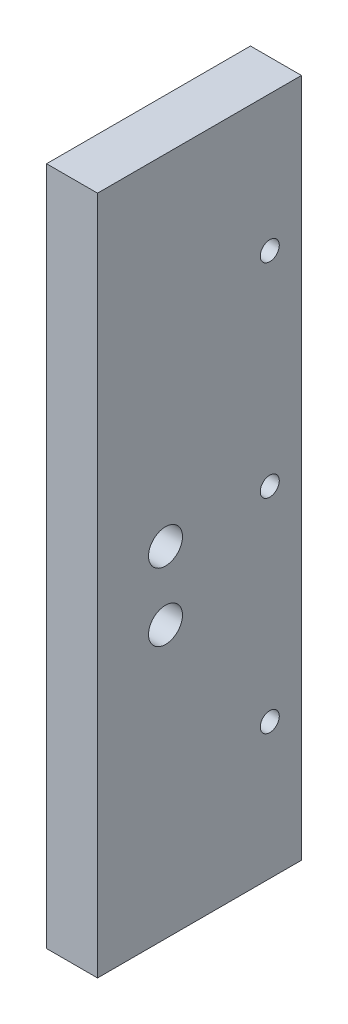
SolidWorks part; units mm, degrees
ref_plane "Front Plane" through (0, 0, 0) normal (0, 0, 1) x (1, 0, 0)
ref_plane "Top Plane" through (0, 0, 0) normal (0, 1, 0) x (1, 0, 0)
ref_plane "Right Plane" through (0, 0, 0) normal (1, 0, 0) x (0, 0, -1)
sketch "Sketch1" plane through (0, 0, 0) normal (0, 0, 1) x (1, 0, 0)
  line L1 (0, 0) -> (9.525, 0)
  line L2 (0, 0) -> (0, 127)
  line L3 (0, 127) -> (9.525, 127)
  line L4 (9.525, 0) -> (9.525, 127)
  dimension "D1" = 9.525
  dimension "D2" = 127
extrude "Boss-Extrude1" add sketch "Sketch1" along normal blind 38.1
sketch "Sketch2" plane through (0, 0, 0) normal (-1, 0, 0) x (0, 0, 1)
  line L0 (5.9182, 127) -> (5.9182, 0) construction
  line L1 (38.1, 127) -> (0, 127) construction
  line L2 (38.1, 0) -> (0, 0) construction
  line L3 (0, 127) -> (0, 0) construction
  circle A0 centre (5.9182, 101.6) radius 1.778
  circle A1 centre (5.9182, 63.5) radius 1.778
  circle A2 centre (5.9182, 25.4) radius 1.778
  dimension "D2" = 3.556
  dimension "D3" = 25.4
  dimension "D1" = 5.9182
  dimension "D4" = 38.1
  dimension "D5" = 38.1
extrude "Cut-Extrude1" cut sketch "Sketch2" against normal through all
sketch "Sketch3" plane through (9.525, 0, 0) normal (1, 0, 0) x (0, 0, -1)
  line L0 (-25.4, 127) -> (-25.4, 0) construction
  line L1 (-38.1, 127) -> (0, 127) construction
  line L2 (-38.1, 0) -> (0, 0) construction
  line L3 (-38.1, 0) -> (-38.1, 127) construction
  circle A0 centre (-25.4, 63.5) radius 3.175
  circle A1 centre (-25.4, 50.8) radius 3.175
  dimension "D1" = 6.35
  dimension "D2" = 6.35
  dimension "D3" = 12.7
  dimension "D4" = 12.7
  dimension "D5" = 63.5
extrude "Cut-Extrude2" cut sketch "Sketch3" against normal blind 38.1
